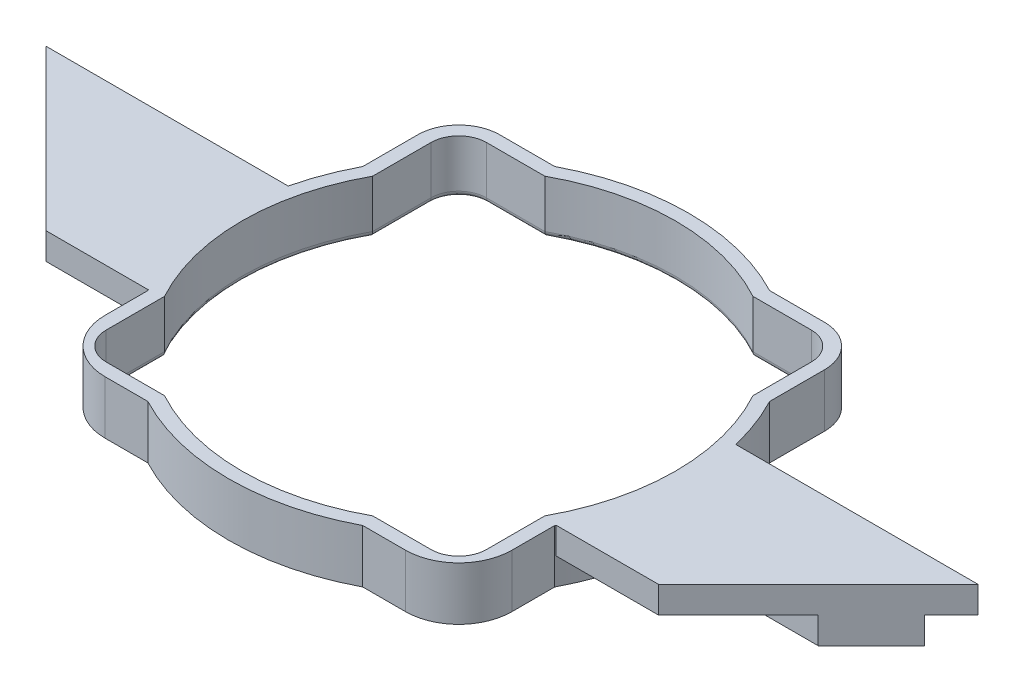
SolidWorks part; units mm, degrees
ref_plane "Front Plane" through (0, 0, 0) normal (0, 0, 1) x (1, 0, 0)
ref_plane "Top Plane" through (0, 0, 0) normal (0, 1, 0) x (1, 0, 0)
ref_plane "Right Plane" through (0, 0, 0) normal (1, 0, 0) x (0, 0, -1)
sketch "Sketch1" plane through (0, 0, 0) normal (0, 1, 0) x (1, 0, 0)
  line L1 (-127, -76.2) -> (127, -76.2)
  line L2 (-127, -76.2) -> (-127, 76.2)
  line L3 (-127, 76.2) -> (127, 76.2)
  line L4 (127, -76.2) -> (127, 76.2)
  line L5 (-127, -76.2) -> (127, 76.2) construction
  line L6 (-127, 76.2) -> (127, -76.2) construction
  point P0 (0, 0)
  dimension "D1" = 254
  dimension "D2" = 152.4
extrude "Boss-Extrude1" add sketch "Sketch1" along normal blind 12.7 contours L2 L3 L4 L1
sketch "Sketch4" plane through (0, 0, 0) normal (0, -1, 0) x (1, 0, 0)
  line L0 (45.339, 24.8219) -> (45.339, 38.735)
  line L1 (38.735, 45.339) -> (24.8219, 45.339)
  line L2 (-24.8219, 45.339) -> (-38.735, 45.339)
  line L3 (-45.339, 38.735) -> (-45.339, 24.8219)
  line L4 (-45.339, -24.8219) -> (-45.339, -38.735)
  line L5 (-38.735, -45.339) -> (-24.8219, -45.339)
  line L6 (24.8219, -45.339) -> (38.735, -45.339)
  line L7 (45.339, -38.735) -> (45.339, -24.8219)
  line L9 (45.085, 24.7569) -> (45.085, 38.735)
  line L10 (38.735, 45.085) -> (24.7569, 45.085)
  line L11 (-24.7569, 45.085) -> (-38.735, 45.085)
  line L12 (-45.085, 38.735) -> (-45.085, 24.7569)
  line L13 (-45.085, -24.7569) -> (-45.085, -38.735)
  line L14 (-38.735, -45.085) -> (-24.7569, -45.085)
  line L15 (24.7569, -45.085) -> (38.735, -45.085)
  line L24 (45.085, -38.735) -> (45.085, -24.7569)
  line L25 (45.085, 24.7569) -> (45.085, 38.735) construction
  line L26 (38.735, 45.085) -> (24.7569, 45.085) construction
  line L27 (-24.7569, 45.085) -> (-38.735, 45.085) construction
  line L28 (-45.085, 38.735) -> (-45.085, 24.7569) construction
  line L29 (-45.085, -24.7569) -> (-45.085, -38.735) construction
  line L30 (-38.735, -45.085) -> (-24.7569, -45.085) construction
  line L31 (24.7569, -45.085) -> (38.735, -45.085) construction
  line L32 (45.085, -38.735) -> (45.085, -24.7569) construction
  line L33 (48.514, 25.6213) -> (48.514, 38.735)
  line L34 (38.735, 48.514) -> (25.6213, 48.514)
  line L35 (-25.6213, 48.514) -> (-38.735, 48.514)
  line L36 (-48.514, 38.735) -> (-48.514, 25.6213)
  line L37 (-48.514, -25.6213) -> (-48.514, -38.735)
  line L38 (-38.735, -48.514) -> (-25.6213, -48.514)
  line L39 (25.6213, -48.514) -> (38.735, -48.514)
  line L40 (48.514, -38.735) -> (48.514, -25.6213)
  arc A0 (45.339, 38.735) -> (38.735, 45.339) centre (38.735, 38.735) ccw
  arc A1 (24.8219, 45.339) -> (-24.8219, 45.339) centre (0, 0) ccw
  arc A2 (-38.735, 45.339) -> (-45.339, 38.735) centre (-38.735, 38.735) ccw
  arc A3 (-45.339, 24.8219) -> (-45.339, -24.8219) centre (0, 0) ccw
  arc A4 (-45.339, -38.735) -> (-38.735, -45.339) centre (-38.735, -38.735) ccw
  arc A5 (-24.8219, -45.339) -> (24.8219, -45.339) centre (0, 0) ccw
  arc A6 (38.735, -45.339) -> (45.339, -38.735) centre (38.735, -38.735) ccw
  arc A7 (45.339, -24.8219) -> (45.339, 24.8219) centre (0, 0) ccw
  arc A24 (45.085, 38.735) -> (38.735, 45.085) centre (38.735, 38.735) ccw
  arc A25 (24.7569, 45.085) -> (-24.7569, 45.085) centre (0, 0) ccw
  arc A26 (-38.735, 45.085) -> (-45.085, 38.735) centre (-38.735, 38.735) ccw
  arc A27 (-45.085, 24.7569) -> (-45.085, -24.7569) centre (0, 0) ccw
  arc A28 (-45.085, -38.735) -> (-38.735, -45.085) centre (-38.735, -38.735) ccw
  arc A29 (-24.7569, -45.085) -> (24.7569, -45.085) centre (0, 0) ccw
  arc A30 (38.735, -45.085) -> (45.085, -38.735) centre (38.735, -38.735) ccw
  arc A31 (45.085, -24.7569) -> (45.085, 24.7569) centre (0, 0) ccw
  arc A32 (45.085, 38.735) -> (38.735, 45.085) centre (38.735, 38.735) ccw construction
  arc A33 (24.7569, 45.085) -> (-24.7569, 45.085) centre (0, 0) ccw construction
  arc A34 (-38.735, 45.085) -> (-45.085, 38.735) centre (-38.735, 38.735) ccw construction
  arc A35 (-45.085, 24.7569) -> (-45.085, -24.7569) centre (0, 0) ccw construction
  arc A36 (-45.085, -38.735) -> (-38.735, -45.085) centre (-38.735, -38.735) ccw construction
  arc A37 (-24.7569, -45.085) -> (24.7569, -45.085) centre (0, 0) ccw construction
  arc A38 (38.735, -45.085) -> (45.085, -38.735) centre (38.735, -38.735) ccw construction
  arc A39 (45.085, -24.7569) -> (45.085, 24.7569) centre (0, 0) ccw construction
  arc A40 (48.514, 38.735) -> (38.735, 48.514) centre (38.735, 38.735) ccw
  arc A41 (25.6213, 48.514) -> (-25.6213, 48.514) centre (0, 0) ccw
  arc A42 (-38.735, 48.514) -> (-48.514, 38.735) centre (-38.735, 38.735) ccw
  arc A43 (-48.514, 25.6213) -> (-48.514, -25.6213) centre (0, 0) ccw
  arc A44 (-48.514, -38.735) -> (-38.735, -48.514) centre (-38.735, -38.735) ccw
  arc A45 (-25.6213, -48.514) -> (25.6213, -48.514) centre (0, 0) ccw
  arc A46 (38.735, -48.514) -> (48.514, -38.735) centre (38.735, -38.735) ccw
  arc A47 (48.514, -25.6213) -> (48.514, 25.6213) centre (0, 0) ccw
  dimension "D1" = 0
  dimension "D2" = 0.254
  dimension "D3" = 3.175
extrude "Cut-Extrude1" cut sketch "Sketch4" against normal through all flip side to cut
sketch "Sketch5" plane through (0, 0, 0) normal (0, 1, 0) x (1, 0, 0)
  line L0 (54.4953, 6.35) -> (104.775, 6.35)
  line L1 (104.775, 6.35) -> (92.075, -6.35)
  line L2 (92.075, -6.35) -> (54.4953, -6.35)
  line L3 (0, 0) -> (0, 33.5108) construction
  line L4 (-92.075, -6.35) -> (-54.4953, -6.35)
  line L5 (-104.775, 6.35) -> (-92.075, -6.35)
  line L6 (-54.4953, 6.35) -> (-104.775, 6.35)
  arc A0 (48.514, -25.6213) -> (48.514, 25.6213) centre (0, 0) ccw construction
  arc A1 (54.4953, -6.35) -> (54.4953, 6.35) centre (0, 0) ccw
  arc A2 (-54.4953, -6.35) -> (-54.4953, 6.35) centre (0, 0) cw
  point P9 (98.425, 0)
  dimension "D1" = 12.7
  dimension "D2" = 104.775
  dimension "D3" = 45
extrude "Boss-Extrude2" add sketch "Sketch5" along normal blind 6.35
sketch "Sketch6" plane through (0, 0, 0) normal (0, 1, 0) x (1, 0, 0)
  line L0 (53.3739, 12.7) -> (111.125, 12.7)
  line L1 (111.125, 12.7) -> (73.025, -25.4)
  line L2 (73.025, -25.4) -> (48.6302, -25.4)
  line L3 (92.075, -6.35) -> (104.775, 6.35) construction
  line L4 (104.775, 6.35) -> (54.4953, 6.35) construction
  line L5 (54.4953, -6.35) -> (92.075, -6.35) construction
  line L6 (0, 0) -> (0, 23.3719) construction
  line L7 (-73.025, -25.4) -> (-48.6302, -25.4)
  line L8 (-111.125, 12.7) -> (-73.025, -25.4)
  line L9 (-53.3739, 12.7) -> (-111.125, 12.7)
  arc A0 (48.514, -25.6213) -> (48.514, 25.6213) centre (0, 0) ccw construction
  arc A1 (48.6302, -25.4) -> (53.3739, 12.7) centre (0, 0) ccw
  arc A2 (-48.6302, -25.4) -> (-53.3739, 12.7) centre (0, 0) cw
  dimension "D1" = 6.35
  dimension "D2" = 19.05
extrude "Boss-Extrude3" add sketch "Sketch6" along normal blind 6.35 from surface starting at face at (76.5523, 6.35, 0)
fillet "Fillet1" radius 1.27 16 edges at (45.339, 0, 31.7785) (43.4047, 0, 43.4047) (-31.7785, 0, 45.339) (-43.4047, 0, 43.4047) (-45.339, 0, -31.7785) (-43.4047, 0, -43.4047) (45.339, 0, -31.7785) (43.4047, 0, -43.4047) (51.689, 0, 0) (31.7785, 0, 45.339) (0, 0, 51.689) (-45.339, 0, 31.7785) (-51.689, 0, 0) (-31.7785, 0, -45.339) (0, 0, -51.689) (31.7785, 0, -45.339)
sketch "Sketch9" plane through (0, 12.7, 0) normal (0, 1, 0) x (1, 0, 0)
  line L0 (48.514, -25.6213) -> (48.514, -38.735) construction
  line L1 (38.735, -48.514) -> (25.6213, -48.514) construction
  line L2 (0, 0) -> (0, -39.3727) construction
  line L3 (38.735, -48.514) -> (35.814, -48.514)
  line L4 (48.514, -35.814) -> (48.514, -38.735)
  line L5 (-48.514, -35.814) -> (-48.514, -38.735)
  line L6 (-38.735, -48.514) -> (-35.814, -48.514)
  arc A0 (35.814, -48.514) -> (48.514, -35.814) centre (35.814, -35.814) ccw
  arc A1 (38.735, -48.514) -> (48.514, -38.735) centre (38.735, -38.735) ccw construction
  arc A2 (38.735, -48.514) -> (48.514, -38.735) centre (38.735, -38.735) ccw
  arc A3 (-38.735, -48.514) -> (-48.514, -38.735) centre (-38.735, -38.735) cw
  arc A4 (-35.814, -48.514) -> (-48.514, -35.814) centre (-35.814, -35.814) cw
  dimension "D1" = 25.4
extrude "Cut-Extrude3" cut sketch "Sketch9" against normal through all
equation "\"tightTol\"= 0.005in"
equation "\"normTol\"= 0.01in"
equation "\"looseTol\"= 0.02in"
equation "\"D2@Sketch4\"=\"normTol\""
